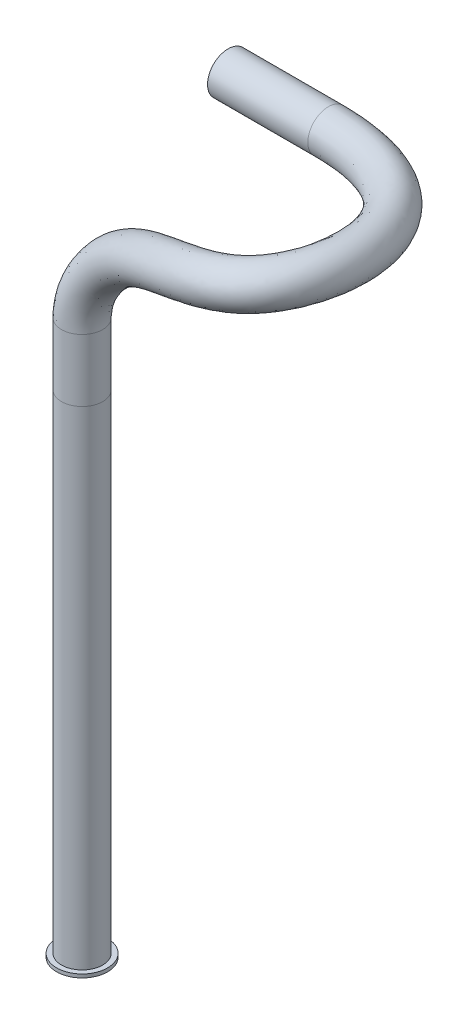
SolidWorks part; units mm, degrees
ref_plane "Front" through (0, 0, 0) normal (0, 0, 1) x (1, 0, 0)
ref_plane "Top" through (0, 0, 0) normal (0, 1, 0) x (1, 0, 0)
ref_plane "Right" through (0, 0, 0) normal (1, 0, 0) x (0, 0, -1)
ref_axis "Axis1" through (0, 0, 55) along (0, 0, -1)
sketch3d "3DSketch1"
  line L0 (-293.0656, 200.9234, 39.5479) -> (-256.5417, 200.9234, 39.5479)
  line L1 (-288.6789, 131.8597, 97.1093) -> (-288.6789, 154.5777, 97.1093)
  line L2 (-288.6789, 131.8597, 97.1093) -> (-288.6789, -47.1266, 97.1093)
  spline S0 degree 3 poles (-288.6789, 154.5777, 97.1093) (-288.6789, 162.2268, 97.1093) (-273.7422, 190.6505, 93.7298) (-194.8397, 216.3396, 142.5128) (-203.5973, 200.9234, 39.5479) (-256.5417, 200.9234, 39.5479) knots 0 0 0 0 0.122904 0.544038 1 1 1 1
  point P7 (0, 0, 0)
  point P8 (0, 0, 0)
  point P9 (0, 0, 0)
  point P10 (0, 0, 0)
  point P11 (0, 0, 0)
  point P12 (0, 0, 0)
  point P13 (0, 0, 0)
ref_plane "Plane1" through (-288.6789, -47.1266, 97.1093) normal (0, -1, 0) x (-1, 0, 0)
sketch "Sketch1" plane through (-288.6789, -47.1266, 97.1093) normal (0, -1, 0) x (-1, 0, 0)
  circle A0 centre (0, 0) radius 5.715
  circle A1 centre (0, 0) radius 7.5
  dimension "D1" = 15
  dimension "D2" = 11.43
sweep "Sweep1" add profiles "Sketch1" path "3DSketch1"
ref_plane "Plane2" through (-282.9056, 0, 0) normal (-1, 0, 0) x (0, 0, 1)
sketch "Sketch5" plane through (-288.6789, -47.1266, 97.1093) normal (0, -1, 0) x (-1, 0, 0)
  circle A0 centre (0, 0) radius 9.2781
  circle A1 centre (0, 0) radius 7.5 construction
  circle A2 centre (0, 0) radius 7.5
  dimension "D1" = 18.5563
extrude "Boss-Extrude2" add sketch "Sketch5" against normal blind 1.27
